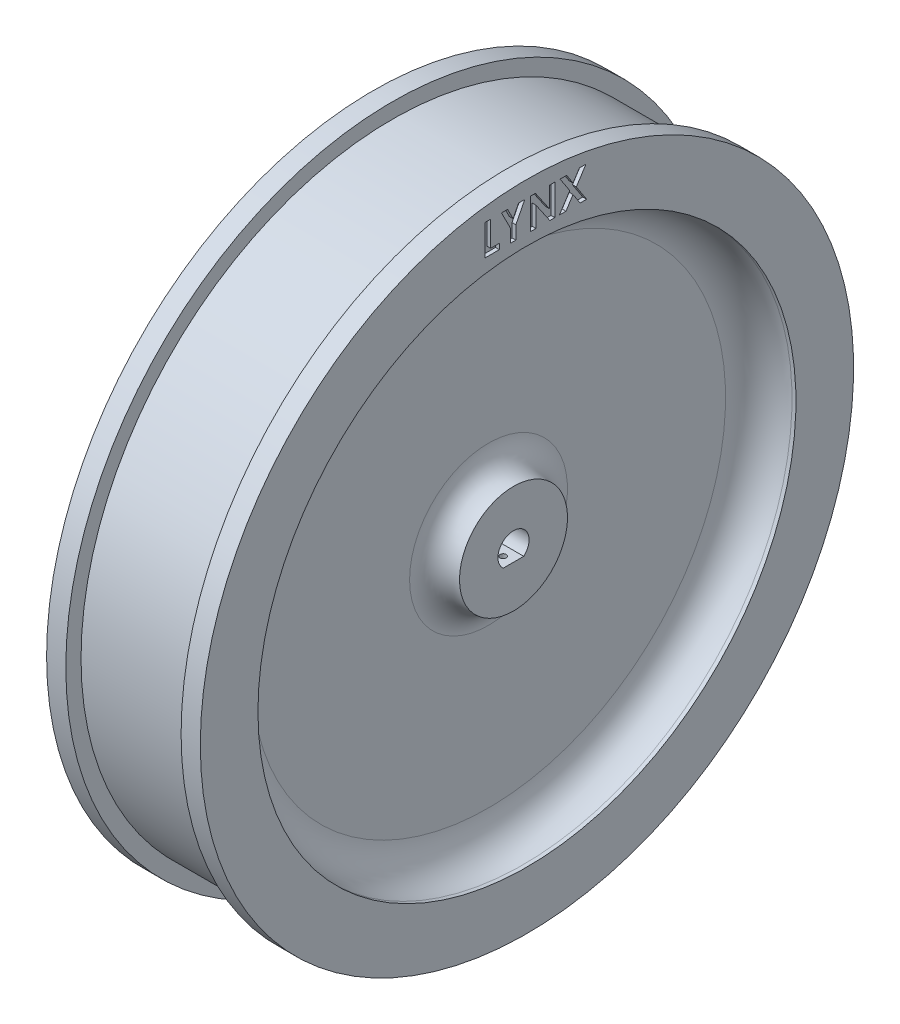
SolidWorks part; units mm, degrees
ref_plane "Front Plane" through (0, 0, 0) normal (0, 0, 1) x (1, 0, 0)
ref_plane "Top Plane" through (0, 0, 0) normal (0, 1, 0) x (1, 0, 0)
ref_plane "Right Plane" through (0, 0, 0) normal (1, 0, 0) x (0, 0, -1)
sketch "Sketch1" plane through (0, 0, 0) normal (0, 0, 1) x (1, 0, 0)
  line L1 (8.9739, 70) -> (10, 70)
  line L2 (10, 70) -> (10, 85)
  line L3 (10, 85) -> (5, 85)
  line L5 (5, 81.0389) -> (-25, 81.0389)
  line L7 (-25, 85) -> (-30, 85)
  line L8 (-30, 85) -> (-30, 70)
  line L9 (-30, 70) -> (-15, 70) construction
  line L10 (-15, 70) -> (-15, 0) construction
  line L12 (0, 0) -> (32.5586, 0) construction
  line L13 (0, 0) -> (0, 98.1963) construction
  line L14 (5, 81.0389) -> (5, 85)
  line L15 (-25, 81.0389) -> (-25, 85)
  line L16 (0, 61.6845) -> (0, 20.54)
  line L17 (6.49, 14.05) -> (6.5, 14.05)
  line L18 (6.5, 14.05) -> (6.5, 4.05)
  line L19 (6.5, 4.05) -> (-9.5, 4.05)
  line L20 (-9.5, 4.05) -> (-9.5, 0)
  line L21 (-9.5, 0) -> (-15, 0)
  line L22 (-15, 0) -> (-15, 10)
  arc A0 (0, 61.6845) -> (8.9739, 70) centre (8.9739, 61) cw
  arc A1 (0, 20.54) -> (6.49, 14.05) centre (6.49, 20.54) ccw
  conic Q0 (-30, 70) -> (-15, 10) control (-18.6357, 58.0621) rho 0.697214
  point P15 (0, 70)
  point P27 (0, 14.05)
  dimension "D1" = 5
  dimension "D2" = 5
  dimension "D11" = 9
  dimension "D16" = 6.49
  dimension "D3" = 30
  dimension "D4" = 15
  dimension "D5" = 15
  dimension "D6" = 10
  dimension "D7" = 10
  dimension "D8" = 15
  dimension "D9" = 4.05
  dimension "D10" = 70
  dimension "D12" = 16
  dimension "D13" = 10
  dimension "D14" = 3.5
  dimension "D15" = 5.5
revolve "Revolve2" add sketch "Sketch1" angle 360 about L12
sketch "Sketch2" plane through (6.5, 0, 0) normal (1, 0, 0) x (0, 0, -1)
  line L0 (0, -3.05) -> (-2.6646, -3.05)
  line L1 (0, -3.05) -> (2.6646, -3.05)
  circle A1 centre (0, 0) radius 4.05 construction
  circle A2 centre (0, 0) radius 4.05 construction
  arc A3 (2.6646, -3.05) -> (-2.6646, -3.05) centre (0, 0) cw
  point P7 (-2.1248, -2.1881)
extrude "Boss-Extrude2" add sketch "Sketch2" against normal blind 16
sketch "Sketch5" plane through (10, 0, 0) normal (1, 0, 0) x (0, 0, -1)
  text T0 "LYNX" font "Century Gothic" height 8
extrude "Cut-Extrude2" cut sketch "Sketch5" against normal blind 1
sketch "Sketch6" plane through (0, -3.05, 0) normal (0, 1, 0) x (1, 0, 0)
  line L0 (6.5, -2.6646) -> (6.5, 2.6646) construction
  line L2 (6.5, 0) -> (1.9421, 0) construction
  circle A0 centre (3.806, 0) radius 0.8
  point P2 (3.806, 0)
extrude "Cut-Extrude4" cut sketch "Sketch6" against normal blind 20
